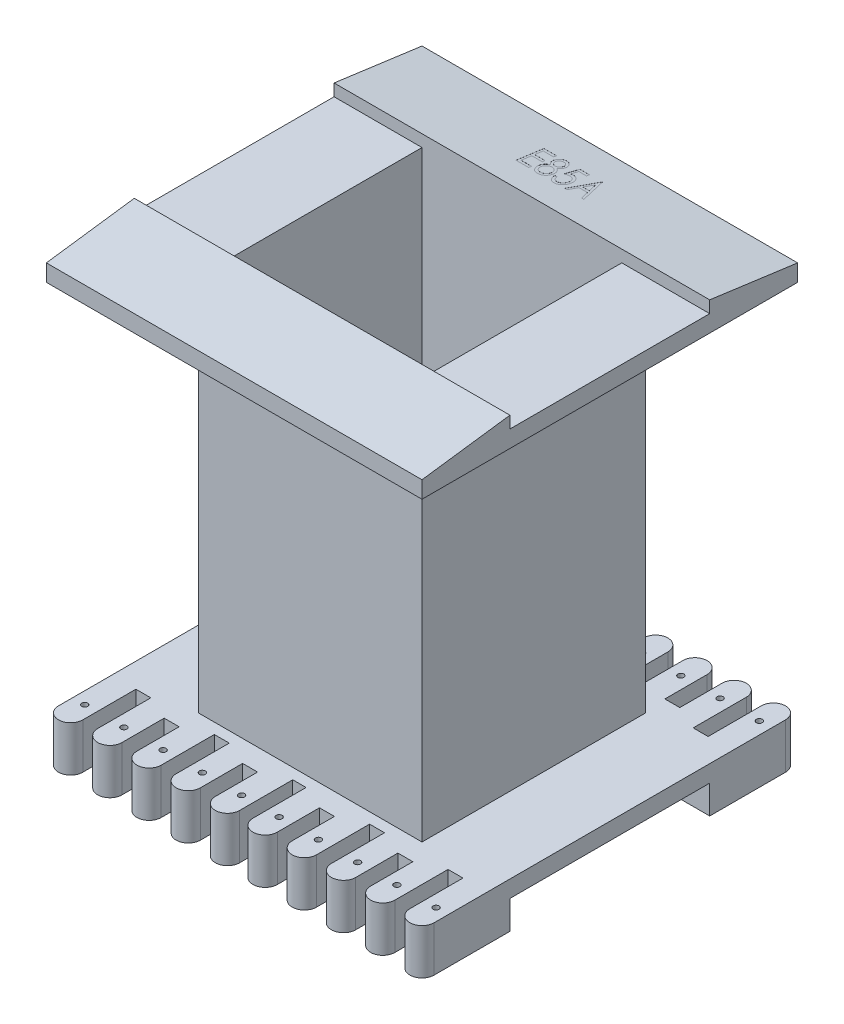
SolidWorks part; units mm, degrees
material "ABS"
ref_plane "Front Plane" through (0, 0, 0) normal (0, 0, 1) x (1, 0, 0)
ref_plane "Top Plane" through (0, 0, 0) normal (0, 1, 0) x (1, 0, 0)
ref_plane "Right Plane" through (0, 0, 0) normal (1, 0, 0) x (0, 0, -1)
sketch "Sketch2" plane through (0, 0, 0) normal (0, 1, 0) x (1, 0, 0)
  line L1 (-15.9, 15.9) -> (15.9, 15.9)
  line L2 (-15.9, 15.9) -> (-15.9, -15.9)
  line L3 (-15.9, -15.9) -> (15.9, -15.9)
  line L4 (15.9, 15.9) -> (15.9, -15.9)
  line L5 (-15.9, 15.9) -> (15.9, -15.9) construction
  line L6 (-15.9, -15.9) -> (15.9, 15.9) construction
  line L7 (-14.2, 14.2) -> (14.2, 14.2)
  line L8 (-14.2, 14.2) -> (-14.2, -14.2)
  line L9 (-14.2, -14.2) -> (14.2, -14.2)
  line L10 (14.2, 14.2) -> (14.2, -14.2)
  line L11 (-14.2, 14.2) -> (14.2, -14.2) construction
  line L12 (-14.2, -14.2) -> (14.2, 14.2) construction
  point P0 (0, 0)
  point P5 (0, 0)
  dimension "D1" = 31.8
  dimension "D2" = 28.4
extrude "Boss-Extrude1" add sketch "Sketch2" along normal mid plane 53
sketch "Sketch4" plane through (0, 26.5, 0) normal (0, 1, 0) x (1, 0, 0)
  line L0 (-14.2, -14.2) -> (14.2, -14.2) construction
  line L1 (-26.7, -26.7) -> (26.7, -26.7)
  line L2 (-26.7, -26.7) -> (-26.7, 26.7)
  line L3 (-26.7, 26.7) -> (26.7, 26.7)
  line L4 (26.7, -26.7) -> (26.7, 26.7)
  line L5 (-26.7, -26.7) -> (26.7, 26.7) construction
  line L6 (-26.7, 26.7) -> (26.7, -26.7) construction
  line L7 (-14.2, 14.2) -> (-14.2, -14.2) construction
  line L8 (14.2, 14.2) -> (-14.2, 14.2) construction
  line L9 (14.2, -14.2) -> (14.2, 14.2) construction
  line L10 (-14.2, -14.2) -> (14.2, -14.2)
  line L11 (-14.2, 14.2) -> (-14.2, -14.2)
  line L12 (14.2, 14.2) -> (-14.2, 14.2)
  line L13 (14.2, -14.2) -> (14.2, 14.2)
  point P0 (0, 0)
  dimension "D1" = 53.4
  dimension "D2" = 53.4
extrude "Boss-Extrude2" add sketch "Sketch4" along normal blind 2.4
mirror "Mirror1" about plane through (0, 0, 0) normal (0, 1, 0) of "Boss-Extrude2"
sketch "Sketch5" plane through (0, 0, 0) normal (1, 0, 0) x (0, 0, -1)
  line L0 (-26.7, 28.9) -> (-14.2, 30.6)
  line L2 (-26.7, 28.9) -> (26.7, 28.9) construction
  line L3 (-14.2, 30.6) -> (-14.2, 28.9)
  line L4 (-14.2, 28.9) -> (-26.7, 28.9)
  line L5 (0, 0) -> (0, 38.1311) construction
  line L6 (14.2, 30.6) -> (14.2, 28.9)
  line L7 (26.7, 28.9) -> (14.2, 30.6)
  line L8 (14.2, 28.9) -> (26.7, 28.9)
  line L9 (-14.2, 28.9) -> (-14.2, -28.9) construction
  point P3 (-14.7578, 30.6)
  point P14 (0, 0)
  point P15 (0, 0)
  dimension "D1" = 1.7
extrude "Boss-Extrude3" add sketch "Sketch5" along normal mid plane 53.4
sketch "Sketch7" plane through (0, -28.9, 0) normal (0, -1, 0) x (1, 0, 0)
  line L0 (0, 35.9012) -> (0, -6.2706) construction
  line L1 (-26.7, 26.7) -> (-26.7, 24.975)
  line L2 (-26.7, -26.7) -> (-26.7, 26.7) construction
  line L3 (-26.7, 26.7) -> (26.7, 26.7) construction
  line L4 (-26.7, 26.7) -> (-26.7, 27.95)
  line L5 (-26.7, 27.95) -> (26.7, 27.95)
  line L6 (-12.1, 24.975) -> (-12.1, 17.425)
  line L7 (26.7, 24.975) -> (-16.1388, 24.975) construction
  line L20 (-23.25, 24.975) -> (-23.25, 17.425)
  line L21 (-23.25, 17.425) -> (-21.125, 17.425)
  line L22 (-21.125, 17.425) -> (-21.125, 24.975)
  line L23 (-21.125, 24.975) -> (-23.25, 24.975) construction
  line L24 (-23.25, 24.975) -> (-26.7, 24.975) construction
  line L28 (-6.525, 24.975) -> (-6.525, 18.975)
  line L29 (-16.1388, 24.975) -> (-21.125, 24.975) construction
  line L30 (-9.975, 17.425) -> (-9.975, 24.975)
  line L31 (-12.1, 17.425) -> (-9.975, 17.425)
  line L32 (-17.675, 24.975) -> (-17.675, 18.975)
  line L33 (-17.675, 18.975) -> (-15.55, 18.975)
  line L34 (-15.55, 18.975) -> (-15.55, 24.975)
  line L35 (-6.525, 18.975) -> (-4.4, 18.975)
  line L36 (-4.4, 18.975) -> (-4.4, 24.975)
  line L37 (16.1388, 24.975) -> (21.125, 24.975) construction
  line L38 (23.25, 24.975) -> (26.7, 24.975) construction
  line L39 (21.125, 24.975) -> (23.25, 24.975) construction
  line L40 (4.4, 18.975) -> (4.4, 24.975)
  line L41 (6.525, 18.975) -> (4.4, 18.975)
  line L42 (15.55, 18.975) -> (15.55, 24.975)
  line L43 (17.675, 18.975) -> (15.55, 18.975)
  line L44 (17.675, 24.975) -> (17.675, 18.975)
  line L45 (12.1, 17.425) -> (9.975, 17.425)
  line L46 (9.975, 17.425) -> (9.975, 24.975)
  line L47 (6.525, 24.975) -> (6.525, 18.975)
  line L48 (21.125, 17.425) -> (21.125, 24.975)
  line L49 (23.25, 17.425) -> (21.125, 17.425)
  line L50 (23.25, 24.975) -> (23.25, 17.425)
  line L51 (12.1, 24.975) -> (12.1, 17.425)
  line L53 (26.7, 27.95) -> (26.7, 24.975)
  line L55 (-0.95, 24.975) -> (-0.95, 17.425)
  line L56 (-0.95, 17.425) -> (0.95, 17.425)
  line L57 (0.95, 17.425) -> (0.95, 24.975)
  line L58 (-24.975, 23.4) -> (-26.02, 23.4) construction
  line L60 (-14.2, 14.2) -> (14.2, 14.2) construction
  line L61 (0, 0) -> (-5.5861, 0) construction
  line L62 (-24.975, -23.4) -> (-26.02, -23.4) construction
  line L63 (21.125, -24.975) -> (23.25, -24.975) construction
  line L64 (23.25, -24.975) -> (26.7, -24.975) construction
  line L65 (16.1388, -24.975) -> (21.125, -24.975) construction
  line L66 (-16.1388, -24.975) -> (-21.125, -24.975) construction
  line L67 (-23.25, -24.975) -> (-26.7, -24.975) construction
  line L68 (-21.125, -24.975) -> (-23.25, -24.975) construction
  line L69 (26.7, -24.975) -> (-16.1388, -24.975) construction
  line L70 (0.95, -17.425) -> (0.95, -24.975)
  line L71 (-0.95, -17.425) -> (0.95, -17.425)
  line L72 (-0.95, -24.975) -> (-0.95, -17.425)
  line L73 (26.7, -27.95) -> (26.7, -24.975)
  line L74 (12.1, -24.975) -> (12.1, -17.425)
  line L75 (23.25, -24.975) -> (23.25, -17.425)
  line L76 (23.25, -17.425) -> (21.125, -17.425)
  line L77 (21.125, -17.425) -> (21.125, -24.975)
  line L78 (6.525, -24.975) -> (6.525, -18.975)
  line L79 (9.975, -17.425) -> (9.975, -24.975)
  line L80 (12.1, -17.425) -> (9.975, -17.425)
  line L81 (17.675, -24.975) -> (17.675, -18.975)
  line L82 (17.675, -18.975) -> (15.55, -18.975)
  line L83 (15.55, -18.975) -> (15.55, -24.975)
  line L84 (6.525, -18.975) -> (4.4, -18.975)
  line L85 (4.4, -18.975) -> (4.4, -24.975)
  line L86 (-4.4, -18.975) -> (-4.4, -24.975)
  line L87 (-6.525, -18.975) -> (-4.4, -18.975)
  line L88 (-15.55, -18.975) -> (-15.55, -24.975)
  line L89 (-17.675, -18.975) -> (-15.55, -18.975)
  line L90 (-17.675, -24.975) -> (-17.675, -18.975)
  line L91 (-12.1, -17.425) -> (-9.975, -17.425)
  line L92 (-9.975, -17.425) -> (-9.975, -24.975)
  line L93 (-6.525, -24.975) -> (-6.525, -18.975)
  line L94 (-21.125, -17.425) -> (-21.125, -24.975)
  line L95 (-23.25, -17.425) -> (-21.125, -17.425)
  line L96 (-23.25, -24.975) -> (-23.25, -17.425)
  line L97 (-12.1, -24.975) -> (-12.1, -17.425)
  line L98 (-26.7, -27.95) -> (26.7, -27.95)
  line L99 (-26.7, -26.7) -> (-26.7, -27.95)
  line L100 (-26.7, -26.7) -> (-26.7, -24.975)
  arc A0 (-26.7, 24.975) -> (-23.25, 24.975) centre (-24.975, 24.975) cw
  arc A11 (-21.125, 24.975) -> (-17.675, 24.975) centre (-19.4, 24.975) cw
  arc A12 (-15.55, 24.975) -> (-12.1, 24.975) centre (-13.825, 24.975) cw
  arc A13 (-9.975, 24.975) -> (-6.525, 24.975) centre (-8.25, 24.975) cw
  arc A14 (-4.4, 24.975) -> (-0.95, 24.975) centre (-2.675, 24.975) cw
  arc A15 (4.4, 24.975) -> (0.95, 24.975) centre (2.675, 24.975) ccw
  arc A16 (9.975, 24.975) -> (6.525, 24.975) centre (8.25, 24.975) ccw
  arc A17 (15.55, 24.975) -> (12.1, 24.975) centre (13.825, 24.975) ccw
  arc A18 (21.125, 24.975) -> (17.675, 24.975) centre (19.4, 24.975) ccw
  arc A19 (26.7, 24.975) -> (23.25, 24.975) centre (24.975, 24.975) ccw
  circle A20 centre (-24.975, 22.975) radius 0.425
  circle A21 centre (-19.4, 22.975) radius 0.425
  circle A22 centre (-13.825, 22.975) radius 0.425
  circle A23 centre (-8.25, 22.975) radius 0.425
  circle A24 centre (-2.675, 22.975) radius 0.425
  circle A25 centre (19.4, 22.975) radius 0.425
  circle A26 centre (13.825, 22.975) radius 0.425
  circle A27 centre (8.25, 22.975) radius 0.425
  circle A28 centre (2.675, 22.975) radius 0.425
  circle A29 centre (24.975, 22.975) radius 0.425
  circle A30 centre (24.975, -22.975) radius 0.425
  circle A31 centre (2.675, -22.975) radius 0.425
  circle A32 centre (8.25, -22.975) radius 0.425
  circle A33 centre (13.825, -22.975) radius 0.425
  circle A34 centre (19.4, -22.975) radius 0.425
  circle A35 centre (-2.675, -22.975) radius 0.425
  circle A36 centre (-8.25, -22.975) radius 0.425
  circle A37 centre (-13.825, -22.975) radius 0.425
  circle A38 centre (-19.4, -22.975) radius 0.425
  circle A39 centre (-24.975, -22.975) radius 0.425
  arc A40 (26.7, -24.975) -> (23.25, -24.975) centre (24.975, -24.975) cw
  arc A41 (21.125, -24.975) -> (17.675, -24.975) centre (19.4, -24.975) cw
  arc A42 (15.55, -24.975) -> (12.1, -24.975) centre (13.825, -24.975) cw
  arc A43 (9.975, -24.975) -> (6.525, -24.975) centre (8.25, -24.975) cw
  arc A44 (4.4, -24.975) -> (0.95, -24.975) centre (2.675, -24.975) cw
  arc A45 (-4.4, -24.975) -> (-0.95, -24.975) centre (-2.675, -24.975) ccw
  arc A46 (-9.975, -24.975) -> (-6.525, -24.975) centre (-8.25, -24.975) ccw
  arc A47 (-15.55, -24.975) -> (-12.1, -24.975) centre (-13.825, -24.975) ccw
  arc A48 (-21.125, -24.975) -> (-17.675, -24.975) centre (-19.4, -24.975) ccw
  arc A49 (-26.7, -24.975) -> (-23.25, -24.975) centre (-24.975, -24.975) ccw
  dimension "D1" = 3.3
  dimension "D6" = 1.25
  dimension "D8" = 0.85
  dimension "D2" = 3.225
  dimension "D3" = 1.55
  dimension "D4" = 6
  dimension "D5" = 2.125
  dimension "D7" = 2
  dimension "D9" = 5
extrude "Cut-Extrude1" cut sketch "Sketch7" against normal blind 3
sketch "Sketch8" plane through (0, -28.9, 0) normal (0, -1, 0) x (1, 0, 0)
  line L0 (-26.7, 14.2) -> (26.7, 14.2)
  line L1 (26.7, 24.975) -> (26.7, -24.975) construction
  line L2 (0, 0) -> (-9.975, 0) construction
  line L3 (-26.7, -24.975) -> (-26.7, -14.2)
  line L8 (-23.25, -17.425) -> (-23.25, -24.975)
  line L9 (-21.125, -17.425) -> (-23.25, -17.425)
  line L10 (-21.125, -24.975) -> (-21.125, -17.425)
  line L11 (-17.675, -18.975) -> (-17.675, -24.975)
  line L12 (-15.55, -18.975) -> (-17.675, -18.975)
  line L13 (-15.55, -24.975) -> (-15.55, -18.975)
  line L14 (-12.1, -17.425) -> (-12.1, -24.975)
  line L15 (-9.975, -17.425) -> (-12.1, -17.425)
  line L16 (-9.975, -24.975) -> (-9.975, -17.425)
  line L17 (-6.525, -18.975) -> (-6.525, -24.975)
  line L18 (-4.4, -18.975) -> (-6.525, -18.975)
  line L19 (-4.4, -24.975) -> (-4.4, -18.975)
  line L20 (-0.95, -17.425) -> (-0.95, -24.975)
  line L21 (0.95, -17.425) -> (-0.95, -17.425)
  line L22 (0.95, -24.975) -> (0.95, -17.425)
  line L23 (4.4, -18.975) -> (4.4, -24.975)
  line L24 (6.525, -18.975) -> (4.4, -18.975)
  line L25 (6.525, -24.975) -> (6.525, -18.975)
  line L26 (9.975, -17.425) -> (9.975, -24.975)
  line L27 (12.1, -17.425) -> (9.975, -17.425)
  line L28 (12.1, -24.975) -> (12.1, -17.425)
  line L29 (15.55, -18.975) -> (15.55, -24.975)
  line L30 (17.675, -18.975) -> (15.55, -18.975)
  line L31 (17.675, -24.975) -> (17.675, -18.975)
  line L32 (21.125, -17.425) -> (21.125, -24.975)
  line L33 (23.25, -17.425) -> (21.125, -17.425)
  line L34 (23.25, -24.975) -> (23.25, -17.425)
  line L35 (26.7, -14.2) -> (26.7, -24.975)
  line L36 (-26.7, -14.2) -> (26.7, -14.2)
  line L58 (26.7, -24.975) -> (26.7, 24.975)
  line L59 (23.25, 24.975) -> (23.25, 17.425)
  line L60 (23.25, 17.425) -> (21.125, 17.425)
  line L61 (21.125, 17.425) -> (21.125, 24.975)
  line L62 (17.675, 24.975) -> (17.675, 18.975)
  line L63 (17.675, 18.975) -> (15.55, 18.975)
  line L64 (15.55, 18.975) -> (15.55, 24.975)
  line L65 (12.1, 24.975) -> (12.1, 17.425)
  line L66 (12.1, 17.425) -> (9.975, 17.425)
  line L67 (9.975, 17.425) -> (9.975, 24.975)
  line L68 (6.525, 24.975) -> (6.525, 18.975)
  line L69 (6.525, 18.975) -> (4.4, 18.975)
  line L70 (4.4, 18.975) -> (4.4, 24.975)
  line L71 (0.95, 24.975) -> (0.95, 17.425)
  line L72 (0.95, 17.425) -> (-0.95, 17.425)
  line L73 (-0.95, 17.425) -> (-0.95, 24.975)
  line L74 (-4.4, 24.975) -> (-4.4, 18.975)
  line L75 (-4.4, 18.975) -> (-6.525, 18.975)
  line L76 (-6.525, 18.975) -> (-6.525, 24.975)
  line L77 (-9.975, 24.975) -> (-9.975, 17.425)
  line L78 (-9.975, 17.425) -> (-12.1, 17.425)
  line L79 (-12.1, 17.425) -> (-12.1, 24.975)
  line L80 (-15.55, 24.975) -> (-15.55, 18.975)
  line L81 (-15.55, 18.975) -> (-17.675, 18.975)
  line L82 (-17.675, 18.975) -> (-17.675, 24.975)
  line L83 (-21.125, 24.975) -> (-21.125, 17.425)
  line L84 (-21.125, 17.425) -> (-23.25, 17.425)
  line L85 (-23.25, 17.425) -> (-23.25, 24.975)
  line L86 (-26.7, 24.975) -> (-26.7, -24.975)
  line L87 (-23.25, -24.975) -> (-23.25, -17.425)
  line L88 (-23.25, -17.425) -> (-21.125, -17.425)
  line L89 (-21.125, -17.425) -> (-21.125, -24.975)
  line L90 (-17.675, -24.975) -> (-17.675, -18.975)
  line L91 (-17.675, -18.975) -> (-15.55, -18.975)
  line L92 (-15.55, -18.975) -> (-15.55, -24.975)
  line L93 (-12.1, -24.975) -> (-12.1, -17.425)
  line L94 (-12.1, -17.425) -> (-9.975, -17.425)
  line L95 (-9.975, -17.425) -> (-9.975, -24.975)
  line L96 (-6.525, -24.975) -> (-6.525, -18.975)
  line L97 (-6.525, -18.975) -> (-4.4, -18.975)
  line L98 (-4.4, -18.975) -> (-4.4, -24.975)
  line L99 (-0.95, -24.975) -> (-0.95, -17.425)
  line L100 (-0.95, -17.425) -> (0.95, -17.425)
  line L101 (0.95, -17.425) -> (0.95, -24.975)
  line L102 (4.4, -24.975) -> (4.4, -18.975)
  line L103 (4.4, -18.975) -> (6.525, -18.975)
  line L104 (6.525, -18.975) -> (6.525, -24.975)
  line L105 (9.975, -24.975) -> (9.975, -17.425)
  line L106 (9.975, -17.425) -> (12.1, -17.425)
  line L107 (12.1, -17.425) -> (12.1, -24.975)
  line L108 (15.55, -24.975) -> (15.55, -18.975)
  line L109 (15.55, -18.975) -> (17.675, -18.975)
  line L110 (17.675, -18.975) -> (17.675, -24.975)
  line L111 (21.125, -24.975) -> (21.125, -17.425)
  line L112 (21.125, -17.425) -> (23.25, -17.425)
  line L113 (23.25, -17.425) -> (23.25, -24.975)
  line L114 (26.7, 14.2) -> (26.7, 24.975)
  line L115 (23.25, 24.975) -> (23.25, 17.425)
  line L116 (23.25, 17.425) -> (21.125, 17.425)
  line L117 (21.125, 17.425) -> (21.125, 24.975)
  line L118 (17.675, 24.975) -> (17.675, 18.975)
  line L119 (17.675, 18.975) -> (15.55, 18.975)
  line L120 (15.55, 18.975) -> (15.55, 24.975)
  line L121 (12.1, 24.975) -> (12.1, 17.425)
  line L122 (12.1, 17.425) -> (9.975, 17.425)
  line L123 (9.975, 17.425) -> (9.975, 24.975)
  line L124 (6.525, 24.975) -> (6.525, 18.975)
  line L125 (6.525, 18.975) -> (4.4, 18.975)
  line L126 (4.4, 18.975) -> (4.4, 24.975)
  line L127 (0.95, 24.975) -> (0.95, 17.425)
  line L128 (0.95, 17.425) -> (-0.95, 17.425)
  line L129 (-0.95, 17.425) -> (-0.95, 24.975)
  line L130 (-4.4, 24.975) -> (-4.4, 18.975)
  line L131 (-4.4, 18.975) -> (-6.525, 18.975)
  line L132 (-6.525, 18.975) -> (-6.525, 24.975)
  line L133 (-9.975, 24.975) -> (-9.975, 17.425)
  line L134 (-9.975, 17.425) -> (-12.1, 17.425)
  line L135 (-12.1, 17.425) -> (-12.1, 24.975)
  line L136 (-15.55, 24.975) -> (-15.55, 18.975)
  line L137 (-15.55, 18.975) -> (-17.675, 18.975)
  line L138 (-17.675, 18.975) -> (-17.675, 24.975)
  line L139 (-21.125, 24.975) -> (-21.125, 17.425)
  line L140 (-21.125, 17.425) -> (-23.25, 17.425)
  line L141 (-23.25, 17.425) -> (-23.25, 24.975)
  line L142 (-26.7, 24.975) -> (-26.7, 14.2)
  arc A0 (-23.25, -24.975) -> (-26.7, -24.975) centre (-24.975, -24.975) cw
  arc A1 (-17.675, -24.975) -> (-21.125, -24.975) centre (-19.4, -24.975) cw
  arc A2 (-12.1, -24.975) -> (-15.55, -24.975) centre (-13.825, -24.975) cw
  arc A3 (-6.525, -24.975) -> (-9.975, -24.975) centre (-8.25, -24.975) cw
  arc A4 (-0.95, -24.975) -> (-4.4, -24.975) centre (-2.675, -24.975) cw
  arc A5 (4.4, -24.975) -> (0.95, -24.975) centre (2.675, -24.975) cw
  arc A6 (9.975, -24.975) -> (6.525, -24.975) centre (8.25, -24.975) cw
  arc A7 (15.55, -24.975) -> (12.1, -24.975) centre (13.825, -24.975) cw
  arc A8 (21.125, -24.975) -> (17.675, -24.975) centre (19.4, -24.975) cw
  arc A9 (26.7, -24.975) -> (23.25, -24.975) centre (24.975, -24.975) cw
  arc A20 (23.25, -24.975) -> (26.7, -24.975) centre (24.975, -24.975) ccw
  arc A21 (26.7, 24.975) -> (23.25, 24.975) centre (24.975, 24.975) ccw
  arc A22 (21.125, 24.975) -> (17.675, 24.975) centre (19.4, 24.975) ccw
  arc A23 (15.55, 24.975) -> (12.1, 24.975) centre (13.825, 24.975) ccw
  arc A24 (9.975, 24.975) -> (6.525, 24.975) centre (8.25, 24.975) ccw
  arc A25 (4.4, 24.975) -> (0.95, 24.975) centre (2.675, 24.975) ccw
  arc A26 (-0.95, 24.975) -> (-4.4, 24.975) centre (-2.675, 24.975) ccw
  arc A27 (-6.525, 24.975) -> (-9.975, 24.975) centre (-8.25, 24.975) ccw
  arc A28 (-12.1, 24.975) -> (-15.55, 24.975) centre (-13.825, 24.975) ccw
  arc A29 (-17.675, 24.975) -> (-21.125, 24.975) centre (-19.4, 24.975) ccw
  arc A30 (-23.25, 24.975) -> (-26.7, 24.975) centre (-24.975, 24.975) ccw
  arc A31 (-26.7, -24.975) -> (-23.25, -24.975) centre (-24.975, -24.975) ccw
  arc A32 (-21.125, -24.975) -> (-17.675, -24.975) centre (-19.4, -24.975) ccw
  arc A33 (-15.55, -24.975) -> (-12.1, -24.975) centre (-13.825, -24.975) ccw
  arc A34 (-9.975, -24.975) -> (-6.525, -24.975) centre (-8.25, -24.975) ccw
  arc A35 (-4.4, -24.975) -> (-0.95, -24.975) centre (-2.675, -24.975) ccw
  arc A36 (0.95, -24.975) -> (4.4, -24.975) centre (2.675, -24.975) ccw
  arc A37 (6.525, -24.975) -> (9.975, -24.975) centre (8.25, -24.975) ccw
  arc A38 (12.1, -24.975) -> (15.55, -24.975) centre (13.825, -24.975) ccw
  arc A39 (17.675, -24.975) -> (21.125, -24.975) centre (19.4, -24.975) ccw
  arc A41 (26.7, 24.975) -> (23.25, 24.975) centre (24.975, 24.975) ccw
  arc A42 (21.125, 24.975) -> (17.675, 24.975) centre (19.4, 24.975) ccw
  arc A43 (15.55, 24.975) -> (12.1, 24.975) centre (13.825, 24.975) ccw
  arc A44 (9.975, 24.975) -> (6.525, 24.975) centre (8.25, 24.975) ccw
  arc A45 (4.4, 24.975) -> (0.95, 24.975) centre (2.675, 24.975) ccw
  arc A46 (-0.95, 24.975) -> (-4.4, 24.975) centre (-2.675, 24.975) ccw
  arc A47 (-6.525, 24.975) -> (-9.975, 24.975) centre (-8.25, 24.975) ccw
  arc A48 (-12.1, 24.975) -> (-15.55, 24.975) centre (-13.825, 24.975) ccw
  arc A49 (-17.675, 24.975) -> (-21.125, 24.975) centre (-19.4, 24.975) ccw
  arc A50 (-23.25, 24.975) -> (-26.7, 24.975) centre (-24.975, 24.975) ccw
  dimension "D1" = 0
extrude "Boss-Extrude4" add sketch "Sketch8" along normal blind 4.05
sketch "Sketch9" plane through (0, 31.9404, -4.3439) normal (0, 0.9909, -0.1348) x (1, 0, 0)
  line L0 (-26.7, 13.9468) -> (26.7, 13.9468) construction
  line L1 (-26.7, 22.5619) -> (-26.7, 9.9468) construction
  line L2 (26.7, 22.5619) -> (26.7, 9.9468) construction
  line L3 (26.7, 9.9468) -> (-26.7, 9.9468) construction
  text T0 "E85A" font "Century Gothic" height 4
  dimension "D1" = 4
extrude "Cut-Extrude2" cut sketch "Sketch9" against normal blind 0.01
